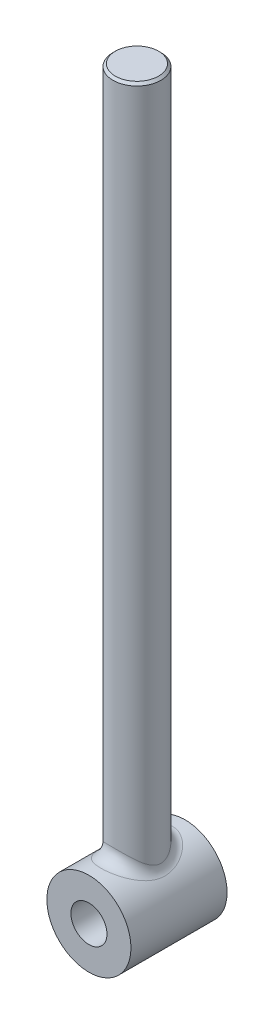
SolidWorks part; units mm, degrees
ref_plane "Front Plane" through (0, 0, 0) normal (0, 0, 1) x (1, 0, 0)
ref_plane "Top Plane" through (0, 0, 0) normal (0, 1, 0) x (1, 0, 0)
ref_plane "Right Plane" through (0, 0, 0) normal (1, 0, 0) x (0, 0, -1)
sketch "Sketch1" plane through (0, 0, 0) normal (0, 0, 1) x (1, 0, 0)
  circle A0 centre (0, 0) radius 7.5
  dimension "D1" = 15
extrude "Extrude-Thin1" add sketch "Sketch1" along normal mid plane 40 thin thin type one direction wall 10
sketch "Sketch2" plane through (0, 0, 0) normal (0, 1, 0) x (1, 0, 0)
  circle A0 centre (0, 0) radius 10
  dimension "D1" = 20
extrude "Boss-Extrude1" add sketch "Sketch2" along normal blind 300
fillet "Fillet1" radius 5 1 edges at (2.9493, 17.2497, 9.5552)
chamfer "Chamfer1" distance 1 angle 45 1 edges at (0, 300, 10)
sketch "Sketch3" plane through (0, 0, 20) normal (0, 0, 1) x (1, 0, 0)
  circle A0 centre (0, 0) radius 7.5 construction
  circle A1 centre (0, 0) radius 7.5
extrude "Cut-Extrude1" cut sketch "Sketch3" against normal through all
